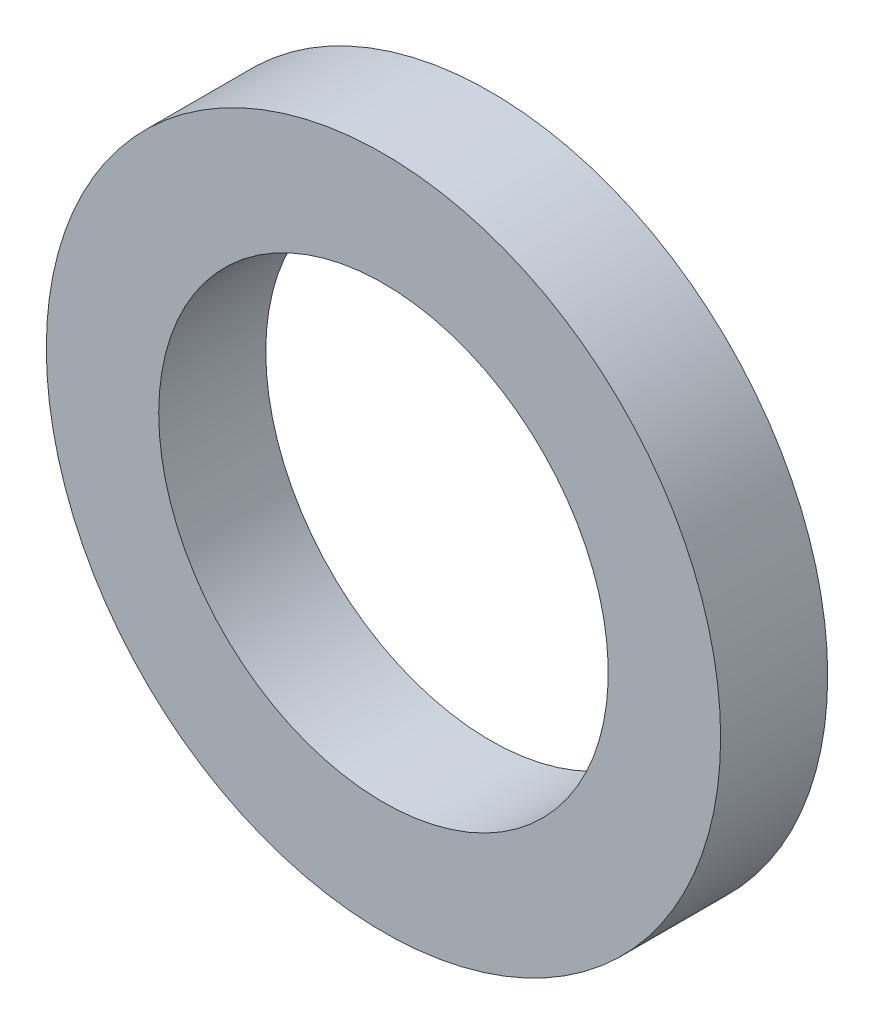
SolidWorks part; units mm, degrees
material "6061-T6 (SS)"
ref_plane "Front Plane" through (0, 0, 0) normal (0, 0, 1) x (1, 0, 0)
ref_plane "Top Plane" through (0, 0, 0) normal (0, 1, 0) x (1, 0, 0)
ref_plane "Right Plane" through (0, 0, 0) normal (1, 0, 0) x (0, 0, -1)
sketch "Sketch1" plane through (0, 0, 0) normal (0, 0, 1) x (1, 0, 0)
  circle A0 centre (0, 0) radius 15
  circle A1 centre (0, 0) radius 10
  dimension "D1" = 30
  dimension "D2" = 20
extrude "Boss-Extrude1" add sketch "Sketch1" along normal mid plane 4.7625
equation "\"D1@Boss-Extrude1\"=3in/16"
